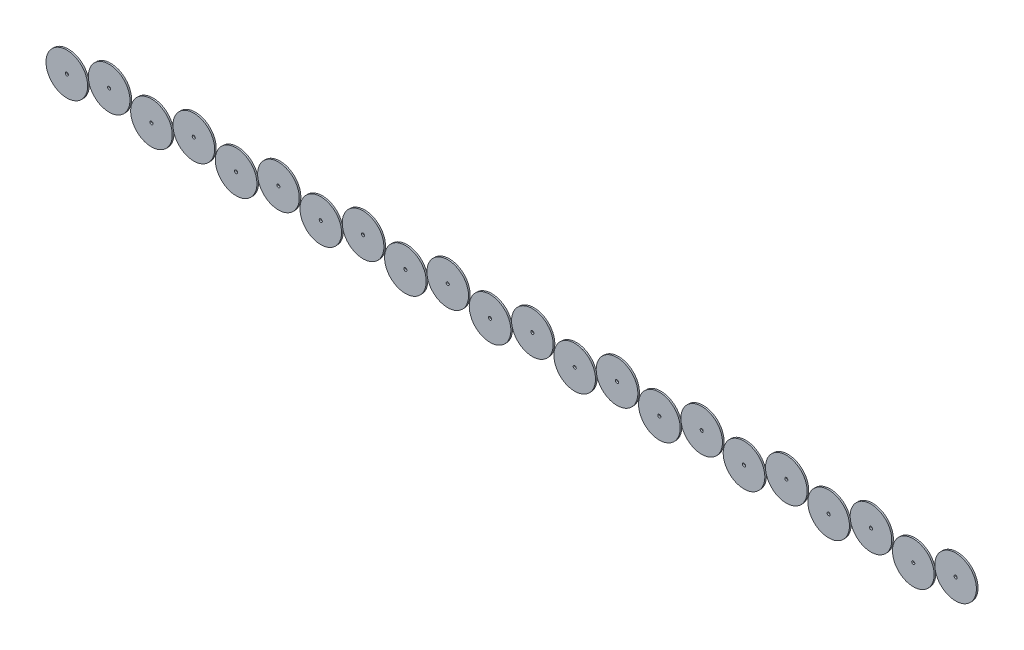
SolidWorks part; units mm, degrees
material "AISI 304"
ref_plane "XY" through (0, 0, 0) normal (0, 0, 1) x (1, 0, 0)
ref_plane "XZ" through (0, 0, 0) normal (0, 1, 0) x (1, 0, 0)
ref_plane "YZ" through (0, 0, 0) normal (1, 0, 0) x (0, 0, -1)
ref_axis "X" through (-88.99, 0, 0) along (1, 0, 0)
ref_axis "Y" through (0, -55, 0) along (0, 1, 0)
ref_axis "Z" through (0, 0, 55) along (0, 0, -1)
sketch "Sketch1" plane through (0, 0, 0) normal (0, 0, 1) x (1, 0, 0)
  line L1 (-457.2, -25.4) -> (457.2, -25.4) construction
  line L2 (-457.2, -25.4) -> (-457.2, 25.4) construction
  line L3 (-457.2, 25.4) -> (457.2, 25.4) construction
  line L4 (457.2, -25.4) -> (457.2, 25.4) construction
  line L5 (-457.2, -25.4) -> (457.2, 25.4) construction
  line L6 (-457.2, 25.4) -> (457.2, -25.4) construction
  circle A0 centre (-435.991, -4.191) radius 19.685
  circle A1 centre (-435.991, -4.191) radius 1.4732
  circle A2 centre (-395.9652, 4.191) radius 19.685
  circle A3 centre (-395.9652, 4.191) radius 1.4732
  circle A4 centre (-355.9395, -4.191) radius 1.4732
  circle A5 centre (-355.9395, -4.191) radius 19.685
  circle A6 centre (-315.9137, 4.191) radius 19.685
  circle A7 centre (-315.9137, 4.191) radius 1.4732
  circle A8 centre (-275.888, -4.191) radius 1.4732
  circle A9 centre (-275.888, -4.191) radius 19.685
  circle A10 centre (-235.8622, 4.191) radius 19.685
  circle A11 centre (-235.8622, 4.191) radius 1.4732
  circle A12 centre (-195.8365, -4.191) radius 1.4732
  circle A13 centre (-195.8365, -4.191) radius 19.685
  circle A14 centre (-155.8107, 4.191) radius 19.685
  circle A15 centre (-155.8107, 4.191) radius 1.4732
  circle A16 centre (-115.7849, -4.191) radius 1.4732
  circle A17 centre (-115.7849, -4.191) radius 19.685
  circle A18 centre (-75.7592, 4.191) radius 19.685
  circle A19 centre (-75.7592, 4.191) radius 1.4732
  circle A20 centre (-35.7334, -4.191) radius 1.4732
  circle A21 centre (-35.7334, -4.191) radius 19.685
  circle A22 centre (4.2923, 4.191) radius 19.685
  circle A23 centre (4.2923, 4.191) radius 1.4732
  circle A24 centre (44.3181, -4.191) radius 1.4732
  circle A25 centre (44.3181, -4.191) radius 19.685
  circle A26 centre (84.3439, 4.191) radius 19.685
  circle A27 centre (84.3439, 4.191) radius 1.4732
  circle A28 centre (124.3696, -4.191) radius 1.4732
  circle A29 centre (124.3696, -4.191) radius 19.685
  circle A30 centre (164.3954, 4.191) radius 19.685
  circle A31 centre (164.3954, 4.191) radius 1.4732
  circle A32 centre (204.4211, -4.191) radius 1.4732
  circle A33 centre (204.4211, -4.191) radius 19.685
  circle A34 centre (244.4469, 4.191) radius 19.685
  circle A35 centre (244.4469, 4.191) radius 1.4732
  circle A36 centre (284.4726, -4.191) radius 1.4732
  circle A37 centre (284.4726, -4.191) radius 19.685
  circle A38 centre (324.4984, 4.191) radius 19.685
  circle A39 centre (324.4984, 4.191) radius 1.4732
  circle A40 centre (364.5242, -4.191) radius 1.4732
  circle A41 centre (364.5242, -4.191) radius 19.685
  circle A42 centre (404.5499, 4.191) radius 19.685
  circle A43 centre (404.5499, 4.191) radius 1.4732
  point P0 (0, 0)
  dimension "D3" = 39.37
  dimension "D4" = 2.9464
  dimension "D5" = 1.524
  dimension "D6" = 1.524
  dimension "D7" = 1.524
  dimension "D8" = 1.524
  dimension "D10" = 1.524
  dimension "D1" = 50.8
  dimension "D2" = 914.4
  dimension "D9" = 11
extrude "Boss-Extrude1" add sketch "Sketch1" along normal blind 1.524
